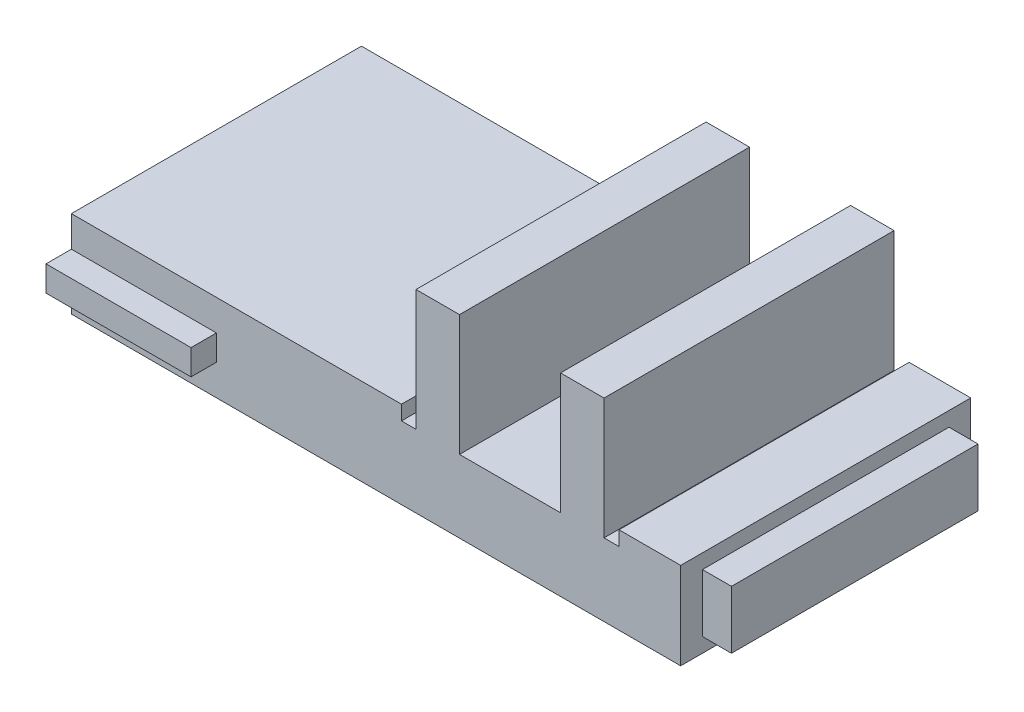
SolidWorks part; units mm, degrees
ref_plane "Front Plane" through (0, 0, 0) normal (0, 0, 1) x (1, 0, 0)
ref_plane "Top Plane" through (0, 0, 0) normal (0, 1, 0) x (1, 0, 0)
ref_plane "Right Plane" through (0, 0, 0) normal (1, 0, 0) x (0, 0, -1)
sketch "Sketch2" plane through (0, 0, 0) normal (0, 0, 1) x (1, 0, 0)
  line L0 (-7.5, 1) -> (-30.26, 1)
  line L1 (-30.26, 1) -> (-30.26, -5)
  line L2 (-30.26, -5) -> (11.75, -5)
  line L3 (11.75, -5) -> (11.75, 1)
  line L4 (11.75, 1) -> (7.5, 1)
  line L5 (7.5, 1) -> (7.5, 0)
  line L6 (7.5, 0) -> (-7.5, 0)
  line L7 (-7.5, 0) -> (-7.5, 1)
  point P2 (0, 0)
  dimension "D1" = 22.76
  dimension "D2" = 5
  dimension "D3" = 1
  dimension "D4" = 15
  dimension "D5" = 4.25
extrude "Boss-Extrude1" add sketch "Sketch2" along normal blind 20
sketch "Sketch6" plane through (11.75, 0, 0) normal (1, 0, 0) x (0, 0, -1)
  line L0 (-20, 1) -> (0, 1) construction
  line L1 (-18.5, 0) -> (-1.5, 0)
  line L2 (-18.5, 0) -> (-18.5, -4)
  line L3 (-18.5, -4) -> (-1.5, -4)
  line L4 (-1.5, 0) -> (-1.5, -4)
  line L5 (-18.5, 0) -> (-1.5, -4) construction
  line L6 (-18.5, -4) -> (-1.5, 0) construction
  line L7 (0, -5) -> (0, 1) construction
  point P0 (-10, -2)
  point P9 (-10, 1)
  point P12 (0, -2)
  dimension "D1" = 4
  dimension "D2" = 17
extrude "Boss-Extrude3" add sketch "Sketch6" along normal blind 2
sketch "Sketch7" plane through (0, 0, 0) normal (0, 1, 0) x (1, 0, 0)
  line L1 (-6.5, 0) -> (-3.5, 0)
  line L2 (-6.5, 0) -> (-6.5, -20)
  line L3 (-6.5, -20) -> (-3.5, -20)
  line L4 (-3.5, 0) -> (-3.5, -20)
  line L5 (-6.5, 0) -> (-3.5, -20) construction
  line L6 (-6.5, -20) -> (-3.5, 0) construction
  line L8 (3.4659, 0) -> (6.4659, 0)
  line L9 (3.4659, 0) -> (3.4659, -20)
  line L10 (7.5, 0) -> (-7.5, 0) construction
  line L11 (7.5, -20) -> (-7.5, -20) construction
  line L12 (3.4659, -20) -> (6.4659, -20)
  line L13 (0, 0) -> (0, -20) construction
  line L18 (-7.5, -20) -> (-7.5, 0) construction
  line L19 (6.4659, 0) -> (6.4659, -20)
  line L20 (3.4659, 0) -> (6.4659, -20) construction
  line L21 (3.4659, -20) -> (6.4659, 0) construction
  point P0 (-5, -10)
  point P5 (4.9659, -10)
  dimension "D1" = 3
  dimension "D2" = 1
  dimension "D3" = 20
  dimension "D4" = 6.9659
extrude "Boss-Extrude4" add sketch "Sketch7" along normal blind 8.35
sketch "Sketch8" plane through (-30.26, 0, 0) normal (-1, 0, 0) x (0, 0, 1)
  line L0 (0, 1) -> (0, -5) construction
  line L1 (-1.75, -1.125) -> (0, -1.125)
  line L2 (-1.75, -1.125) -> (-1.75, -2.875)
  line L3 (-1.75, -2.875) -> (0, -2.875)
  line L4 (0, -1.125) -> (0, -2.875)
  line L5 (-1.75, -1.125) -> (0, -2.875) construction
  line L6 (-1.75, -2.875) -> (0, -1.125) construction
  line L7 (10, 1) -> (10, -5) construction
  line L8 (20, 1) -> (0, 1) construction
  line L9 (20, -5) -> (0, -5) construction
  line L10 (21.75, -2.875) -> (20, -1.125) construction
  line L11 (21.75, -1.125) -> (20, -2.875) construction
  line L12 (20, -1.125) -> (20, -2.875)
  line L13 (21.75, -2.875) -> (20, -2.875)
  line L14 (21.75, -1.125) -> (21.75, -2.875)
  line L15 (21.75, -1.125) -> (20, -1.125)
  point P0 (-0.875, -2)
  point P7 (0, -2)
  point P8 (0, -2)
  point P19 (20.875, -2)
  dimension "D1" = 1.75
extrude "Boss-Extrude5" add sketch "Sketch8" against normal blind 10
